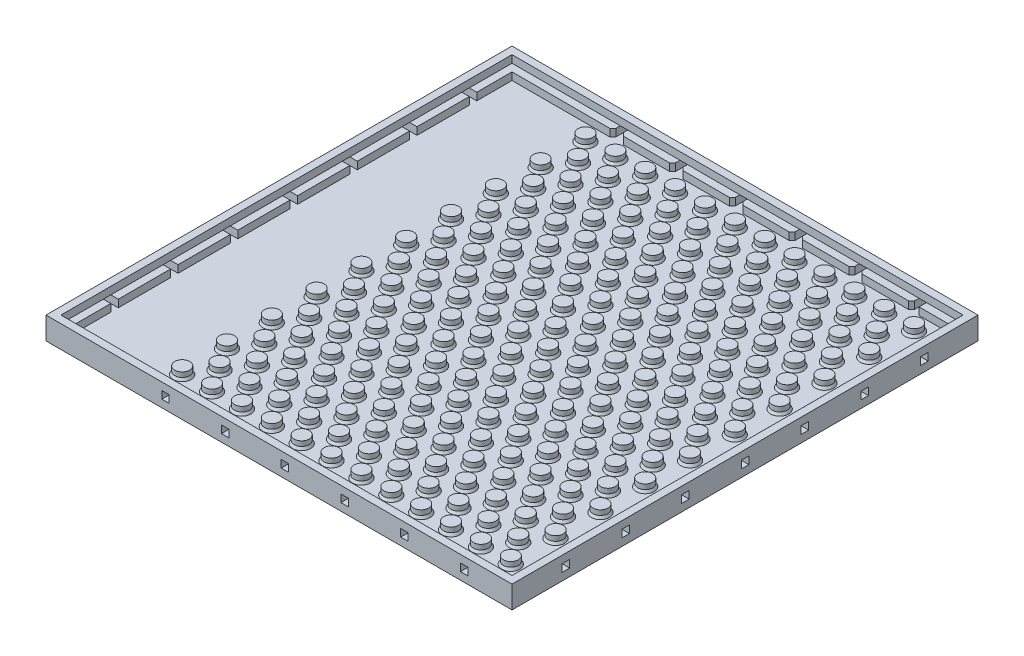
SolidWorks part; units mm, degrees
ref_plane "Front Plane" through (0, 0, 0) normal (0, 0, 1) x (1, 0, 0)
ref_plane "Top Plane" through (0, 0, 0) normal (0, 1, 0) x (1, 0, 0)
ref_plane "Right Plane" through (0, 0, 0) normal (1, 0, 0) x (0, 0, -1)
sketch "Outer_Shell" plane through (0, 0, 0) normal (0, 1, 0) x (1, 0, 0)
  line L0 (41.275, 61.5043) -> (96.52, 61.5043)
  line L1 (-101.6, 61.5043) -> (-41.275, 61.5043)
  line L2 (-101.6, 61.5043) -> (-101.6, -136.6157)
  line L3 (-101.6, -136.6157) -> (4.445, -136.6157)
  line L4 (96.52, 61.5043) -> (96.52, 51.9793)
  line L5 (-9.525, 61.5043) -> (9.525, 61.5043)
  line L6 (-34.925, 61.5043) -> (-15.875, 61.5043)
  line L7 (15.875, 61.5043) -> (34.925, 61.5043)
  line L8 (96.52, -30.5707) -> (96.52, -136.6157)
  line L9 (96.52, 45.6293) -> (96.52, 26.5793)
  line L10 (96.52, 20.2293) -> (96.52, 1.1793)
  line L11 (96.52, -5.1707) -> (96.52, -24.2207)
  line L12 (86.995, -136.6157) -> (96.52, -136.6157)
  line L13 (61.595, -136.6157) -> (80.645, -136.6157)
  line L14 (10.795, -136.6157) -> (29.845, -136.6157)
  line L15 (36.195, -136.6157) -> (55.245, -136.6157)
  line L16 (-41.275, 61.5043) -> (-34.925, 61.5043)
  line L17 (-15.875, 61.5043) -> (-9.525, 61.5043)
  line L18 (9.525, 61.5043) -> (15.875, 61.5043)
  line L19 (34.925, 61.5043) -> (41.275, 61.5043)
  line L20 (96.52, 51.9793) -> (96.52, 45.6293)
  line L21 (96.52, 26.5793) -> (96.52, 20.2293)
  line L22 (96.52, 1.1793) -> (96.52, -5.1707)
  line L23 (96.52, -24.2207) -> (96.52, -30.5707)
  line L24 (86.995, -136.6157) -> (80.645, -136.6157)
  line L25 (61.595, -136.6157) -> (55.245, -136.6157)
  line L26 (36.195, -136.6157) -> (29.845, -136.6157)
  line L27 (10.795, -136.6157) -> (4.445, -136.6157)
  dimension "D1" = 101.6
  dimension "D2" = 198.12
  dimension "D3" = 198.12
extrude "Outer_Shell_Extrusion" add sketch "Outer_Shell" along normal blind 9.525
ref_plane "Plane1" through (0, 0, -10.7043) normal (0, 0, -1) x (-1, 0, 0)
shell "Shell2" thickness 6.35
sketch "Sketch2" plane through (-101.6, 0, 0) normal (-1, 0, 0) x (0, 0, 1)
  line L3 (-61.5043, 9.525) -> (-61.5043, 0) construction
  line L4 (-40.1683, 3.175) -> (-36.9933, 3.175)
  line L5 (-40.1683, 3.175) -> (-40.1683, 6.3754)
  line L6 (-40.1683, 6.3754) -> (-36.9933, 6.3754)
  line L7 (-36.9933, 3.175) -> (-36.9933, 6.3754)
  line L8 (-61.5043, 0) -> (136.6157, 0) construction
  line L9 (-14.7683, 3.175) -> (-11.5933, 3.175)
  line L10 (-14.7683, 3.175) -> (-14.7683, 6.3754)
  line L11 (-14.7683, 6.3754) -> (-11.5933, 6.3754)
  line L12 (-11.5933, 3.175) -> (-11.5933, 6.3754)
  line L13 (10.6317, 3.175) -> (13.8067, 3.175)
  line L14 (10.6317, 3.175) -> (10.6317, 6.3754)
  line L15 (10.6317, 6.3754) -> (13.8067, 6.3754)
  line L16 (13.8067, 3.175) -> (13.8067, 6.3754)
  line L17 (36.0317, 3.175) -> (39.2067, 3.175)
  line L18 (36.0317, 3.175) -> (36.0317, 6.3754)
  line L19 (36.0317, 6.3754) -> (39.2067, 6.3754)
  line L20 (39.2067, 3.175) -> (39.2067, 6.3754)
  line L21 (61.4317, 3.175) -> (64.6067, 3.175)
  line L22 (61.4317, 3.175) -> (61.4317, 6.3754)
  line L23 (61.4317, 6.3754) -> (64.6067, 6.3754)
  line L24 (64.6067, 3.175) -> (64.6067, 6.3754)
  line L25 (86.8317, 3.175) -> (90.0067, 3.175)
  line L26 (86.8317, 3.175) -> (86.8317, 6.3754)
  line L27 (86.8317, 6.3754) -> (90.0067, 6.3754)
  line L28 (90.0067, 3.175) -> (90.0067, 6.3754)
  line L29 (112.2317, 3.175) -> (115.4067, 3.175)
  line L30 (112.2317, 3.175) -> (112.2317, 6.3754)
  line L31 (112.2317, 6.3754) -> (115.4067, 6.3754)
  line L32 (115.4067, 3.175) -> (115.4067, 6.3754)
  dimension "D1" = 7
  dimension "D5" = 21.336
  dimension "D6" = 3.175
  dimension "D7" = 3.2004
  dimension "D8" = 3.175
extrude "Insertion_holes" cut sketch "Sketch2" against normal up to next
sketch "Sketch4" plane through (0, 9.525, 0) normal (0, 1, 0) x (1, 0, 0)
  line L0 (-101.6, 61.5043) -> (-101.6, -136.6157) construction
  line L1 (-98.425, 58.3293) -> (93.345, 58.3293)
  line L2 (-98.425, 58.3293) -> (-98.425, -133.4407)
  line L3 (-98.425, -133.4407) -> (93.345, -133.4407)
  line L4 (93.345, 58.3293) -> (93.345, -133.4407)
  line L5 (96.52, 61.5043) -> (-101.6, 61.5043) construction
  line L6 (96.52, -136.6157) -> (96.52, 61.5043) construction
  line L7 (-101.6, -136.6157) -> (96.52, -136.6157) construction
  dimension "D1" = 3.175
  dimension "D2" = 3.175
  dimension "D3" = 3.175
  dimension "D4" = 3.175
sketch "Sketch3" plane through (0, 3.175, 0) normal (0, 1, 0) x (1, 0, 0)
  line L0 (-101.6, 61.5043) -> (-101.6, -136.6157) construction
  line L4 (-101.6, -136.6157) -> (96.52, -136.6157) construction
  circle A0 centre (-57.15, -123.1537) radius 3.175
  circle A1 centre (-50.8, -113.6287) radius 3.175
  circle A2 centre (-44.45, -123.1537) radius 3.175
  circle A3 centre (-38.1, -113.6287) radius 3.175
  circle A4 centre (-31.75, -123.1537) radius 3.175
  circle A5 centre (-25.4, -113.6287) radius 3.175
  circle A6 centre (-19.05, -123.1537) radius 3.175
  circle A7 centre (-12.7, -113.6287) radius 3.175
  circle A8 centre (-6.35, -123.1537) radius 3.175
  circle A9 centre (0, -113.6287) radius 3.175
  circle A10 centre (6.35, -123.1537) radius 3.175
  circle A11 centre (12.7, -113.6287) radius 3.175
  circle A12 centre (19.05, -123.1537) radius 3.175
  circle A13 centre (25.4, -113.6287) radius 3.175
  circle A14 centre (31.75, -123.1537) radius 3.175
  circle A15 centre (38.1, -113.6287) radius 3.175
  circle A16 centre (44.45, -123.1537) radius 3.175
  circle A17 centre (50.8, -113.6287) radius 3.175
  circle A18 centre (57.15, -123.1537) radius 3.175
  circle A19 centre (63.5, -113.6287) radius 3.175
  circle A20 centre (69.85, -123.1537) radius 3.175
  circle A21 centre (76.2, -113.6287) radius 3.175
  circle A22 centre (-44.45, -104.1037) radius 3.175
  circle A23 centre (-38.1, -94.5787) radius 3.175
  circle A24 centre (-31.75, -104.1037) radius 3.175
  circle A25 centre (-25.4, -94.5787) radius 3.175
  circle A26 centre (-19.05, -104.1037) radius 3.175
  circle A27 centre (-12.7, -94.5787) radius 3.175
  circle A28 centre (-6.35, -104.1037) radius 3.175
  circle A29 centre (0, -94.5787) radius 3.175
  circle A30 centre (6.35, -104.1037) radius 3.175
  circle A31 centre (12.7, -94.5787) radius 3.175
  circle A32 centre (19.05, -104.1037) radius 3.175
  circle A33 centre (25.4, -94.5787) radius 3.175
  circle A34 centre (31.75, -104.1037) radius 3.175
  circle A35 centre (38.1, -94.5787) radius 3.175
  circle A36 centre (44.45, -104.1037) radius 3.175
  circle A37 centre (50.8, -94.5787) radius 3.175
  circle A38 centre (57.15, -104.1037) radius 3.175
  circle A39 centre (63.5, -94.5787) radius 3.175
  circle A40 centre (69.85, -104.1037) radius 3.175
  circle A41 centre (76.2, -94.5787) radius 3.175
  circle A42 centre (-44.45, -85.0537) radius 3.175
  circle A43 centre (-38.1, -75.5287) radius 3.175
  circle A44 centre (-31.75, -85.0537) radius 3.175
  circle A45 centre (-25.4, -75.5287) radius 3.175
  circle A46 centre (-19.05, -85.0537) radius 3.175
  circle A47 centre (-12.7, -75.5287) radius 3.175
  circle A48 centre (-6.35, -85.0537) radius 3.175
  circle A49 centre (0, -75.5287) radius 3.175
  circle A50 centre (6.35, -85.0537) radius 3.175
  circle A51 centre (12.7, -75.5287) radius 3.175
  circle A52 centre (19.05, -85.0537) radius 3.175
  circle A53 centre (25.4, -75.5287) radius 3.175
  circle A54 centre (31.75, -85.0537) radius 3.175
  circle A55 centre (38.1, -75.5287) radius 3.175
  circle A56 centre (44.45, -85.0537) radius 3.175
  circle A57 centre (50.8, -75.5287) radius 3.175
  circle A58 centre (57.15, -85.0537) radius 3.175
  circle A59 centre (63.5, -75.5287) radius 3.175
  circle A60 centre (69.85, -85.0537) radius 3.175
  circle A61 centre (76.2, -75.5287) radius 3.175
  circle A62 centre (-44.45, -66.0037) radius 3.175
  circle A63 centre (-38.1, -56.4787) radius 3.175
  circle A64 centre (-31.75, -66.0037) radius 3.175
  circle A65 centre (-25.4, -56.4787) radius 3.175
  circle A66 centre (-19.05, -66.0037) radius 3.175
  circle A67 centre (-12.7, -56.4787) radius 3.175
  circle A68 centre (-6.35, -66.0037) radius 3.175
  circle A69 centre (0, -56.4787) radius 3.175
  circle A70 centre (6.35, -66.0037) radius 3.175
  circle A71 centre (12.7, -56.4787) radius 3.175
  circle A72 centre (19.05, -66.0037) radius 3.175
  circle A73 centre (25.4, -56.4787) radius 3.175
  circle A74 centre (31.75, -66.0037) radius 3.175
  circle A75 centre (38.1, -56.4787) radius 3.175
  circle A76 centre (44.45, -66.0037) radius 3.175
  circle A77 centre (50.8, -56.4787) radius 3.175
  circle A78 centre (57.15, -66.0037) radius 3.175
  circle A79 centre (63.5, -56.4787) radius 3.175
  circle A80 centre (69.85, -66.0037) radius 3.175
  circle A81 centre (76.2, -56.4787) radius 3.175
  circle A82 centre (-44.45, -46.9537) radius 3.175
  circle A83 centre (-38.1, -37.4287) radius 3.175
  circle A84 centre (-31.75, -46.9537) radius 3.175
  circle A85 centre (-25.4, -37.4287) radius 3.175
  circle A86 centre (-19.05, -46.9537) radius 3.175
  circle A87 centre (-12.7, -37.4287) radius 3.175
  circle A88 centre (-6.35, -46.9537) radius 3.175
  circle A89 centre (0, -37.4287) radius 3.175
  circle A90 centre (6.35, -46.9537) radius 3.175
  circle A91 centre (12.7, -37.4287) radius 3.175
  circle A92 centre (19.05, -46.9537) radius 3.175
  circle A93 centre (25.4, -37.4287) radius 3.175
  circle A94 centre (31.75, -46.9537) radius 3.175
  circle A95 centre (38.1, -37.4287) radius 3.175
  circle A96 centre (44.45, -46.9537) radius 3.175
  circle A97 centre (50.8, -37.4287) radius 3.175
  circle A98 centre (57.15, -46.9537) radius 3.175
  circle A99 centre (63.5, -37.4287) radius 3.175
  circle A100 centre (69.85, -46.9537) radius 3.175
  circle A101 centre (76.2, -37.4287) radius 3.175
  circle A102 centre (-44.45, -27.9037) radius 3.175
  circle A103 centre (-38.1, -18.3787) radius 3.175
  circle A104 centre (-31.75, -27.9037) radius 3.175
  circle A105 centre (-25.4, -18.3787) radius 3.175
  circle A106 centre (-19.05, -27.9037) radius 3.175
  circle A107 centre (-12.7, -18.3787) radius 3.175
  circle A108 centre (-6.35, -27.9037) radius 3.175
  circle A109 centre (0, -18.3787) radius 3.175
  circle A110 centre (6.35, -27.9037) radius 3.175
  circle A111 centre (12.7, -18.3787) radius 3.175
  circle A112 centre (19.05, -27.9037) radius 3.175
  circle A113 centre (25.4, -18.3787) radius 3.175
  circle A114 centre (31.75, -27.9037) radius 3.175
  circle A115 centre (38.1, -18.3787) radius 3.175
  circle A116 centre (44.45, -27.9037) radius 3.175
  circle A117 centre (50.8, -18.3787) radius 3.175
  circle A118 centre (57.15, -27.9037) radius 3.175
  circle A119 centre (63.5, -18.3787) radius 3.175
  circle A120 centre (69.85, -27.9037) radius 3.175
  circle A121 centre (76.2, -18.3787) radius 3.175
  circle A122 centre (-44.45, -8.8537) radius 3.175
  circle A123 centre (-38.1, 0.6713) radius 3.175
  circle A124 centre (-31.75, -8.8537) radius 3.175
  circle A125 centre (-25.4, 0.6713) radius 3.175
  circle A126 centre (-19.05, -8.8537) radius 3.175
  circle A127 centre (-12.7, 0.6713) radius 3.175
  circle A128 centre (-6.35, -8.8537) radius 3.175
  circle A129 centre (0, 0.6713) radius 3.175
  circle A130 centre (6.35, -8.8537) radius 3.175
  circle A131 centre (12.7, 0.6713) radius 3.175
  circle A132 centre (19.05, -8.8537) radius 3.175
  circle A133 centre (25.4, 0.6713) radius 3.175
  circle A134 centre (31.75, -8.8537) radius 3.175
  circle A135 centre (38.1, 0.6713) radius 3.175
  circle A136 centre (44.45, -8.8537) radius 3.175
  circle A137 centre (50.8, 0.6713) radius 3.175
  circle A138 centre (57.15, -8.8537) radius 3.175
  circle A139 centre (63.5, 0.6713) radius 3.175
  circle A140 centre (69.85, -8.8537) radius 3.175
  circle A141 centre (76.2, 0.6713) radius 3.175
  circle A142 centre (-44.45, 10.1963) radius 3.175
  circle A143 centre (-38.1, 19.7213) radius 3.175
  circle A144 centre (-31.75, 10.1963) radius 3.175
  circle A145 centre (-25.4, 19.7213) radius 3.175
  circle A146 centre (-19.05, 10.1963) radius 3.175
  circle A147 centre (-12.7, 19.7213) radius 3.175
  circle A148 centre (-6.35, 10.1963) radius 3.175
  circle A149 centre (0, 19.7213) radius 3.175
  circle A150 centre (6.35, 10.1963) radius 3.175
  circle A151 centre (12.7, 19.7213) radius 3.175
  circle A152 centre (19.05, 10.1963) radius 3.175
  circle A153 centre (25.4, 19.7213) radius 3.175
  circle A154 centre (31.75, 10.1963) radius 3.175
  circle A155 centre (38.1, 19.7213) radius 3.175
  circle A156 centre (44.45, 10.1963) radius 3.175
  circle A157 centre (50.8, 19.7213) radius 3.175
  circle A158 centre (57.15, 10.1963) radius 3.175
  circle A159 centre (63.5, 19.7213) radius 3.175
  circle A160 centre (69.85, 10.1963) radius 3.175
  circle A161 centre (76.2, 19.7213) radius 3.175
  circle A162 centre (-44.45, 29.2463) radius 3.175
  circle A163 centre (-38.1, 38.7713) radius 3.175
  circle A164 centre (-31.75, 29.2463) radius 3.175
  circle A165 centre (-25.4, 38.7713) radius 3.175
  circle A166 centre (-19.05, 29.2463) radius 3.175
  circle A167 centre (-12.7, 38.7713) radius 3.175
  circle A168 centre (-6.35, 29.2463) radius 3.175
  circle A169 centre (0, 38.7713) radius 3.175
  circle A170 centre (6.35, 29.2463) radius 3.175
  circle A171 centre (12.7, 38.7713) radius 3.175
  circle A172 centre (19.05, 29.2463) radius 3.175
  circle A173 centre (25.4, 38.7713) radius 3.175
  circle A174 centre (31.75, 29.2463) radius 3.175
  circle A175 centre (38.1, 38.7713) radius 3.175
  circle A176 centre (44.45, 29.2463) radius 3.175
  circle A177 centre (50.8, 38.7713) radius 3.175
  circle A178 centre (57.15, 29.2463) radius 3.175
  circle A179 centre (63.5, 38.7713) radius 3.175
  circle A180 centre (69.85, 29.2463) radius 3.175
  circle A181 centre (76.2, 38.7713) radius 3.175
  circle A182 centre (-44.45, 48.2963) radius 3.175
  circle A184 centre (-31.75, 48.2963) radius 3.175
  circle A186 centre (-19.05, 48.2963) radius 3.175
  circle A188 centre (-6.35, 48.2963) radius 3.175
  circle A190 centre (6.35, 48.2963) radius 3.175
  circle A192 centre (19.05, 48.2963) radius 3.175
  circle A194 centre (31.75, 48.2963) radius 3.175
  circle A196 centre (44.45, 48.2963) radius 3.175
  circle A198 centre (57.15, 48.2963) radius 3.175
  circle A200 centre (69.85, 48.2963) radius 3.175
  circle A202 centre (-57.15, -104.1037) radius 3.175
  circle A203 centre (-50.8, -94.5787) radius 3.175
  circle A204 centre (-57.15, -85.0537) radius 3.175
  circle A205 centre (-50.8, -75.5287) radius 3.175
  circle A206 centre (-57.15, -66.0037) radius 3.175
  circle A207 centre (-50.8, -56.4787) radius 3.175
  circle A208 centre (-57.15, -46.9537) radius 3.175
  circle A209 centre (-50.8, -37.4287) radius 3.175
  circle A210 centre (-57.15, -27.9037) radius 3.175
  circle A211 centre (-50.8, -18.3787) radius 3.175
  circle A212 centre (-57.15, -8.8537) radius 3.175
  circle A213 centre (-50.8, 0.6713) radius 3.175
  circle A214 centre (-57.15, 10.1963) radius 3.175
  circle A215 centre (-50.8, 19.7213) radius 3.175
  circle A216 centre (-57.15, 29.2463) radius 3.175
  circle A217 centre (-50.8, 38.7713) radius 3.175
  circle A218 centre (-57.15, 48.2963) radius 3.175
  circle A220 centre (82.55, -123.1537) radius 3.175
  circle A221 centre (82.55, -104.1037) radius 3.175
  circle A222 centre (82.55, -85.0537) radius 3.175
  circle A223 centre (82.55, -66.0037) radius 3.175
  circle A224 centre (82.55, -46.9537) radius 3.175
  circle A225 centre (82.55, -27.9037) radius 3.175
  circle A226 centre (82.55, -8.8537) radius 3.175
  circle A227 centre (82.55, 10.1963) radius 3.175
  circle A228 centre (82.55, 29.2463) radius 3.175
  circle A229 centre (82.55, 48.2963) radius 3.175
  circle A230 centre (-50.8, 57.8213) radius 3.175
  circle A231 centre (-38.1, 57.8213) radius 3.175
  circle A232 centre (-25.4, 57.8213) radius 3.175
  circle A233 centre (-12.7, 57.8213) radius 3.175
  circle A234 centre (0, 57.8213) radius 3.175
  circle A235 centre (12.7, 57.8213) radius 3.175
  circle A236 centre (25.4, 57.8213) radius 3.175
  circle A237 centre (38.1, 57.8213) radius 3.175
  circle A238 centre (50.8, 57.8213) radius 3.175
  circle A239 centre (63.5, 57.8213) radius 3.175
  circle A240 centre (76.2, 57.8213) radius 3.175
  dimension "D1" = 6.35
  dimension "D5" = 6.35
  dimension "D6" = 9.525
  dimension "D7" = 11
  dimension "D8" = 10
  dimension "D3" = 6.35
  dimension "D2" = 44.45
  dimension "D4" = 13.462
  dimension "D9" = 2
extrude "Boss-Extrude2" add sketch "Sketch3" along normal blind 3.175
extrude "Cut-Extrude3" cut sketch "Sketch4" against normal blind 3.1725
sketch "Sketch5" plane through (0, 0, 136.6157) normal (0, 0, 1) x (1, 0, 0)
  line L0 (-101.6, 9.525) -> (-101.6, 0) construction
  line L1 (-101.6, 0) -> (96.52, 0) construction
  line L3 (-52.3875, 3.175) -> (-49.2125, 3.175)
  line L4 (-52.3875, 3.175) -> (-52.3875, 6.3754)
  line L5 (-52.3875, 6.3754) -> (-49.2125, 6.3754)
  line L6 (-49.2125, 3.175) -> (-49.2125, 6.3754)
  line L7 (-26.9875, 3.175) -> (-23.8125, 3.175)
  line L8 (-26.9875, 3.175) -> (-26.9875, 6.3754)
  line L9 (-26.9875, 6.3754) -> (-23.8125, 6.3754)
  line L10 (-23.8125, 3.175) -> (-23.8125, 6.3754)
  line L11 (-1.5875, 3.175) -> (1.5875, 3.175)
  line L12 (-1.5875, 3.175) -> (-1.5875, 6.3754)
  line L13 (-1.5875, 6.3754) -> (1.5875, 6.3754)
  line L14 (1.5875, 3.175) -> (1.5875, 6.3754)
  line L15 (23.8125, 3.175) -> (26.9875, 3.175)
  line L16 (23.8125, 3.175) -> (23.8125, 6.3754)
  line L17 (23.8125, 6.3754) -> (26.9875, 6.3754)
  line L18 (26.9875, 3.175) -> (26.9875, 6.3754)
  line L19 (49.2125, 3.175) -> (52.3875, 3.175)
  line L20 (49.2125, 3.175) -> (49.2125, 6.3754)
  line L21 (49.2125, 6.3754) -> (52.3875, 6.3754)
  line L22 (52.3875, 3.175) -> (52.3875, 6.3754)
  line L23 (74.6125, 3.175) -> (77.7875, 3.175)
  line L24 (74.6125, 3.175) -> (74.6125, 6.3754)
  line L25 (74.6125, 6.3754) -> (77.7875, 6.3754)
  line L26 (77.7875, 3.175) -> (77.7875, 6.3754)
  dimension "D1" = 3.2004
  dimension "D2" = 6
  dimension "D5" = 3.175
  dimension "D6" = 3.175
  dimension "D7" = 49.2125
sketch "Sketch6" plane through (96.52, 0, 0) normal (1, 0, 0) x (0, 0, -1)
  line L0 (-136.6157, 9.525) -> (-136.6157, 0) construction
  line L1 (-136.6157, 0) -> (61.5043, 0) construction
  line L2 (-89.8797, 3.175) -> (-86.7047, 3.175)
  line L3 (-115.2797, 3.175) -> (-112.1047, 3.175)
  line L4 (-115.2797, 3.175) -> (-115.2797, 6.3754)
  line L5 (-115.2797, 6.3754) -> (-112.1047, 6.3754)
  line L6 (-112.1047, 3.175) -> (-112.1047, 6.3754)
  line L7 (-86.7047, 3.175) -> (-86.7047, 6.3754)
  line L8 (-89.8797, 6.3754) -> (-86.7047, 6.3754)
  line L9 (-89.8797, 3.175) -> (-89.8797, 6.3754)
  line L10 (-64.4797, 3.175) -> (-61.3047, 3.175)
  line L11 (-61.3047, 3.175) -> (-61.3047, 6.3754)
  line L12 (-64.4797, 6.3754) -> (-61.3047, 6.3754)
  line L13 (-64.4797, 3.175) -> (-64.4797, 6.3754)
  line L14 (-39.0797, 3.175) -> (-35.9047, 3.175)
  line L15 (-35.9047, 3.175) -> (-35.9047, 6.3754)
  line L16 (-39.0797, 6.3754) -> (-35.9047, 6.3754)
  line L17 (-39.0797, 3.175) -> (-39.0797, 6.3754)
  line L18 (-13.6797, 3.175) -> (-10.5047, 3.175)
  line L19 (-10.5047, 3.175) -> (-10.5047, 6.3754)
  line L20 (-13.6797, 6.3754) -> (-10.5047, 6.3754)
  line L21 (-13.6797, 3.175) -> (-13.6797, 6.3754)
  line L22 (11.7203, 3.175) -> (14.8953, 3.175)
  line L23 (14.8953, 3.175) -> (14.8953, 6.3754)
  line L24 (11.7203, 6.3754) -> (14.8953, 6.3754)
  line L25 (11.7203, 3.175) -> (11.7203, 6.3754)
  line L26 (37.1203, 3.175) -> (40.2953, 3.175)
  line L27 (40.2953, 3.175) -> (40.2953, 6.3754)
  line L28 (37.1203, 6.3754) -> (40.2953, 6.3754)
  line L29 (37.1203, 3.175) -> (37.1203, 6.3754)
  dimension "D1" = 7
  dimension "D5" = 3.175
  dimension "D6" = 3.175
  dimension "D7" = 3.2004
  dimension "D8" = 21.336
sketch "Sketch7" plane through (0, 0, -61.5043) normal (0, 0, -1) x (-1, 0, 0)
  line L0 (101.6, 9.525) -> (101.6, 0) construction
  line L1 (49.2125, 3.175) -> (52.3875, 3.175)
  line L2 (49.2125, 3.175) -> (49.2125, 6.3754)
  line L3 (49.2125, 6.3754) -> (52.3875, 6.3754)
  line L4 (52.3875, 3.175) -> (52.3875, 6.3754)
  line L5 (-96.52, 0) -> (101.6, 0) construction
  line L6 (23.8125, 3.175) -> (26.9875, 3.175)
  line L7 (26.9875, 3.175) -> (26.9875, 6.3754)
  line L8 (23.8125, 6.3754) -> (26.9875, 6.3754)
  line L9 (23.8125, 3.175) -> (23.8125, 6.3754)
  line L10 (-1.5875, 3.175) -> (1.5875, 3.175)
  line L11 (1.5875, 3.175) -> (1.5875, 6.3754)
  line L12 (-1.5875, 6.3754) -> (1.5875, 6.3754)
  line L13 (-1.5875, 3.175) -> (-1.5875, 6.3754)
  line L14 (-26.9875, 3.175) -> (-23.8125, 3.175)
  line L15 (-23.8125, 3.175) -> (-23.8125, 6.3754)
  line L16 (-26.9875, 6.3754) -> (-23.8125, 6.3754)
  line L17 (-26.9875, 3.175) -> (-26.9875, 6.3754)
  line L18 (-52.3875, 3.175) -> (-49.2125, 3.175)
  line L19 (-49.2125, 3.175) -> (-49.2125, 6.3754)
  line L20 (-52.3875, 6.3754) -> (-49.2125, 6.3754)
  line L21 (-52.3875, 3.175) -> (-52.3875, 6.3754)
  line L22 (-77.7875, 3.175) -> (-74.6125, 3.175)
  line L23 (-74.6125, 3.175) -> (-74.6125, 6.3754)
  line L24 (-77.7875, 6.3754) -> (-74.6125, 6.3754)
  line L25 (-77.7875, 3.175) -> (-77.7875, 6.3754)
  point P19 (50.8, 3.175)
  dimension "D2" = 3.175
  dimension "D3" = 3.2004
  dimension "D4" = 49.2125
  dimension "D5" = 3.175
  dimension "D1" = 6
extrude "Exit Hole1" cut sketch "Sketch5" against normal up to next
extrude "Exit Hole2" cut sketch "Sketch7" against normal up to next
extrude "Exit Hole3" cut sketch "Sketch6" against normal up to next
chamfer "Chamfer2" distance 1.27 angle 45 37 edges at (23.8125, 4.7638, 130.2657) (26.9875, 4.7638, 130.2657) (49.2125, 4.7638, 130.2657) (52.3875, 4.7638, 130.2657) (74.6125, 4.7638, 130.2657) (77.7875, 4.7638, 130.2657) (90.17, 4.7638, 112.1047) (90.17, 4.7638, 115.2797) (-26.9875, 4.7638, 130.2657) (-23.8125, 4.7638, 130.2657) (-1.5875, 4.7638, 130.2657) (1.5875, 4.7638, 130.2657) (-49.2125, 4.7638, 130.2657) (-52.3875, 4.7638, 130.2657) (90.17, 4.7638, 89.8797) (90.17, 4.7638, 86.7047) (90.17, 4.7638, 64.4797) (90.17, 4.7638, 61.3047) (90.17, 4.7638, 39.0797) (90.17, 4.7638, 35.9047) (90.17, 4.7638, 13.6797) (90.17, 4.7638, 10.5047) (90.17, 4.7638, -37.1203) (90.17, 4.7638, -40.2953) (74.6125, 4.7638, -55.1543) (49.2125, 4.7638, -55.1543) (52.3875, 4.7638, -55.1543) (26.9875, 4.7638, -55.1543) (23.8125, 4.7638, -55.1543) (-1.5875, 4.7638, -55.1543) (1.5875, 4.7638, -55.1543) (-23.8125, 4.7638, -55.1543) (-26.9875, 4.7638, -55.1543) (-52.3875, 4.7638, -55.1543) (-49.2125, 4.7638, -55.1543) (90.17, 4.7638, -14.8953) (90.17, 4.7638, -11.7203)
chamfer "Chamfer3" distance 0.635 angle 60 219 edges at (-57.15, 3.175, 126.3287) (19.05, 3.175, -26.0713) (12.7, 3.175, -35.5963) (6.35, 3.175, -26.0713) (0, 3.175, -35.5963) (44.45, 3.175, -26.0713) (38.1, 3.175, -35.5963) (31.75, 3.175, -26.0713) (25.4, 3.175, -35.5963) (-31.75, 3.175, -26.0713) (-38.1, 3.175, -35.5963) (-44.45, 3.175, -26.0713) (76.2, 3.175, -16.5463) (-6.35, 3.175, -26.0713) (-12.7, 3.175, -35.5963) (-19.05, 3.175, -26.0713) (-25.4, 3.175, -35.5963) (-6.35, 3.175, -45.1213) (6.35, 3.175, -45.1213) (19.05, 3.175, -45.1213) (31.75, 3.175, -45.1213) (-57.15, 3.175, 107.2787) (69.85, 3.175, -45.1213) (57.15, 3.175, -45.1213) (44.45, 3.175, -45.1213) (69.85, 3.175, -26.0713) (63.5, 3.175, -35.5963) (57.15, 3.175, -26.0713) (50.8, 3.175, -35.5963) (-19.05, 3.175, -45.1213) (-31.75, 3.175, -45.1213) (-44.45, 3.175, -45.1213) (76.2, 3.175, -35.5963) (69.85, 3.175, 12.0287) (63.5, 3.175, 2.5037) (57.15, 3.175, 12.0287) (50.8, 3.175, 2.5037) (-31.75, 3.175, -7.0213) (-38.1, 3.175, -16.5463) (-44.45, 3.175, -7.0213) (76.2, 3.175, 2.5037) (19.05, 3.175, 12.0287) (12.7, 3.175, 2.5037) (6.35, 3.175, 12.0287) (0, 3.175, 2.5037) (44.45, 3.175, 12.0287) (38.1, 3.175, 2.5037) (31.75, 3.175, 12.0287) (25.4, 3.175, 2.5037) (44.45, 3.175, -7.0213) (38.1, 3.175, -16.5463) (31.75, 3.175, -7.0213) (25.4, 3.175, -16.5463) (69.85, 3.175, -7.0213) (63.5, 3.175, -16.5463) (57.15, 3.175, -7.0213) (50.8, 3.175, -16.5463) (-6.35, 3.175, -7.0213) (-12.7, 3.175, -16.5463) (-19.05, 3.175, -7.0213) (-25.4, 3.175, -16.5463) (19.05, 3.175, -7.0213) (12.7, 3.175, -16.5463) (6.35, 3.175, -7.0213) (0, 3.175, -16.5463) (-50.8, 3.175, 97.7537) (-57.15, 3.175, 88.2287) (-50.8, 3.175, 78.7037) (-57.15, 3.175, 69.1787) (-50.8, 3.175, 59.6537) (-57.15, 3.175, 50.1287) (-50.8, 3.175, 40.6037) (-57.15, 3.175, 31.0787) (-50.8, 3.175, 21.5537) (-57.15, 3.175, 12.0287) (-50.8, 3.175, 2.5037) (-57.15, 3.175, -7.0213) (-50.8, 3.175, -16.5463) (-57.15, 3.175, -26.0713) (-50.8, 3.175, -35.5963) (82.55, 3.175, 126.3287) (82.55, 3.175, 107.2787) (82.55, 3.175, 88.2287) (82.55, 3.175, 69.1787) (82.55, 3.175, 50.1287) (82.55, 3.175, 31.0787) (82.55, 3.175, 12.0287) (82.55, 3.175, -7.0213) (82.55, 3.175, -45.1213) (82.55, 3.175, -26.0713) (-31.75, 3.175, 88.2287) (-38.1, 3.175, 78.7037) (-44.45, 3.175, 88.2287) (76.2, 3.175, 97.7537) (-6.35, 3.175, 88.2287) (-12.7, 3.175, 78.7037) (-19.05, 3.175, 88.2287) (-25.4, 3.175, 78.7037) (44.45, 3.175, 107.2787) (38.1, 3.175, 97.7537) (31.75, 3.175, 107.2787) (25.4, 3.175, 97.7537) (69.85, 3.175, 107.2787) (63.5, 3.175, 97.7537) (57.15, 3.175, 107.2787) (50.8, 3.175, 97.7537) (69.85, 3.175, 88.2287) (63.5, 3.175, 78.7037) (57.15, 3.175, 88.2287) (50.8, 3.175, 78.7037) (-31.75, 3.175, 69.1787) (-38.1, 3.175, 59.6537) (-44.45, 3.175, 69.1787) (76.2, 3.175, 78.7037) (19.05, 3.175, 88.2287) (12.7, 3.175, 78.7037) (6.35, 3.175, 88.2287) (0, 3.175, 78.7037) (44.45, 3.175, 88.2287) (38.1, 3.175, 78.7037) (31.75, 3.175, 88.2287) (25.4, 3.175, 78.7037) (19.05, 3.175, 126.3287) (12.7, 3.175, 116.8037) (6.35, 3.175, 126.3287) (0, 3.175, 116.8037) (44.45, 3.175, 126.3287) (38.1, 3.175, 116.8037) (31.75, 3.175, 126.3287) (25.4, 3.175, 116.8037) (-31.75, 3.175, 126.3287) (-38.1, 3.175, 116.8037) (-44.45, 3.175, 126.3287) (-50.8, 3.175, 116.8037) (-6.35, 3.175, 126.3287) (-12.7, 3.175, 116.8037) (-19.05, 3.175, 126.3287) (-25.4, 3.175, 116.8037) (-6.35, 3.175, 107.2787) (-12.7, 3.175, 97.7537) (-19.05, 3.175, 107.2787) (-25.4, 3.175, 97.7537) (19.05, 3.175, 107.2787) (12.7, 3.175, 97.7537) (6.35, 3.175, 107.2787) (0, 3.175, 97.7537) (69.85, 3.175, 126.3287) (63.5, 3.175, 116.8037) (57.15, 3.175, 126.3287) (50.8, 3.175, 116.8037) (-31.75, 3.175, 107.2787) (-38.1, 3.175, 97.7537) (-44.45, 3.175, 107.2787) (76.2, 3.175, 116.8037) (-6.35, 3.175, 31.0787) (-12.7, 3.175, 21.5537) (-19.05, 3.175, 31.0787) (-25.4, 3.175, 21.5537) (19.05, 3.175, 31.0787) (12.7, 3.175, 21.5537) (6.35, 3.175, 31.0787) (0, 3.175, 21.5537) (69.85, 3.175, 50.1287) (63.5, 3.175, 40.6037) (57.15, 3.175, 50.1287) (50.8, 3.175, 40.6037) (-31.75, 3.175, 31.0787) (-38.1, 3.175, 21.5537) (-44.45, 3.175, 31.0787) (76.2, 3.175, 40.6037) (-31.75, 3.175, 12.0287) (-38.1, 3.175, 2.5037) (-44.45, 3.175, 12.0287) (76.2, 3.175, 21.5537) (-6.35, 3.175, 12.0287) (-12.7, 3.175, 2.5037) (-19.05, 3.175, 12.0287) (-25.4, 3.175, 2.5037) (44.45, 3.175, 31.0787) (38.1, 3.175, 21.5537) (31.75, 3.175, 31.0787) (25.4, 3.175, 21.5537) (69.85, 3.175, 31.0787) (63.5, 3.175, 21.5537) (57.15, 3.175, 31.0787) (50.8, 3.175, 21.5537) (44.45, 3.175, 69.1787) (38.1, 3.175, 59.6537) (31.75, 3.175, 69.1787) (25.4, 3.175, 59.6537) (69.85, 3.175, 69.1787) (63.5, 3.175, 59.6537) (57.15, 3.175, 69.1787) (50.8, 3.175, 59.6537) (-6.35, 3.175, 69.1787) (-12.7, 3.175, 59.6537) (-19.05, 3.175, 69.1787) (-25.4, 3.175, 59.6537) (19.05, 3.175, 69.1787) (12.7, 3.175, 59.6537) (6.35, 3.175, 69.1787) (0, 3.175, 59.6537) (19.05, 3.175, 50.1287) (12.7, 3.175, 40.6037) (6.35, 3.175, 50.1287) (0, 3.175, 40.6037) (44.45, 3.175, 50.1287) (38.1, 3.175, 40.6037) (31.75, 3.175, 50.1287) (25.4, 3.175, 40.6037) (-31.75, 3.175, 50.1287) (-38.1, 3.175, 40.6037) (-44.45, 3.175, 50.1287) (76.2, 3.175, 59.6537) (-6.35, 3.175, 50.1287) (-12.7, 3.175, 40.6037) (-19.05, 3.175, 50.1287) (-25.4, 3.175, 40.6037) (-57.15, 3.175, -45.1213)
